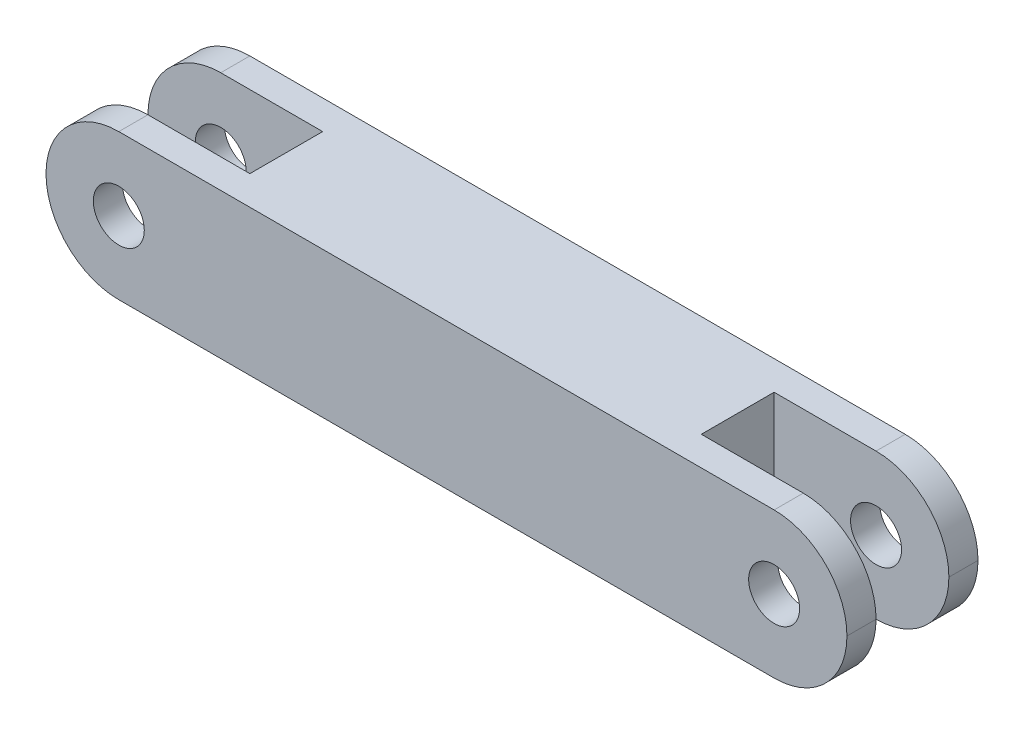
SolidWorks part; units mm, degrees
ref_plane "前视基准面" through (0, 0, 0) normal (0, 0, 1) x (1, 0, 0)
ref_plane "上视基准面" through (0, 0, 0) normal (0, 1, 0) x (1, 0, 0)
ref_plane "右视基准面" through (0, 0, 0) normal (1, 0, 0) x (0, 0, -1)
other "Configuration Table"
sketch "草图5" plane through (0, 0, 0) normal (0, 1, 0) x (1, 0, 0)
  line L0 (0, 0) -> (0, -9)
  line L4 (55, -9) -> (55, 0)
  line L8 (55, 0) -> (0, 0)
  line L9 (0, -9) -> (55, -9)
  dimension "D1" = 55
  dimension "D2" = 9
extrude "凸台-拉伸1" add sketch "草图5" along normal blind 10
fillet "圆角2" radius 5 4 edges at (55, 0, 4.5) (55, 10, 4.5) (0, 0, 4.5) (0, 10, 4.5)
sketch "草图6" plane through (0, 0, 9) normal (0, 0, 1) x (1, 0, 0)
  circle A0 centre (5, 5) radius 1.75
  circle A1 centre (50, 5) radius 1.75
  dimension "D1" = 3.5
extrude "切除-拉伸1" cut sketch "草图6" against normal up to next
sketch "草图7" plane through (0, 0, 0) normal (0, 1, 0) x (1, 0, 0)
  line L0 (0, -4.5) -> (55, -4.5) construction
  line L1 (0, -9) -> (0, 0) construction
  line L2 (55, 0) -> (55, -9) construction
  line L4 (12, -7) -> (0, -7)
  line L5 (12, -7) -> (12, -2)
  line L6 (12, -2) -> (0, -2)
  line L7 (0, -7) -> (0, -2)
  line L8 (12, -7) -> (0, -2) construction
  line L9 (12, -2) -> (0, -7) construction
  line L10 (43, -7) -> (55, -7)
  line L11 (43, -7) -> (43, -2)
  line L12 (43, -2) -> (55, -2)
  line L13 (55, -7) -> (55, -2)
  line L14 (43, -7) -> (55, -2) construction
  line L15 (43, -2) -> (55, -7) construction
  point P6 (6, -4.5)
  point P11 (49, -4.5)
  dimension "D1" = 5
  dimension "D2" = 12
extrude "切除-拉伸4" cut sketch "草图7" against normal through all and the other way through all
